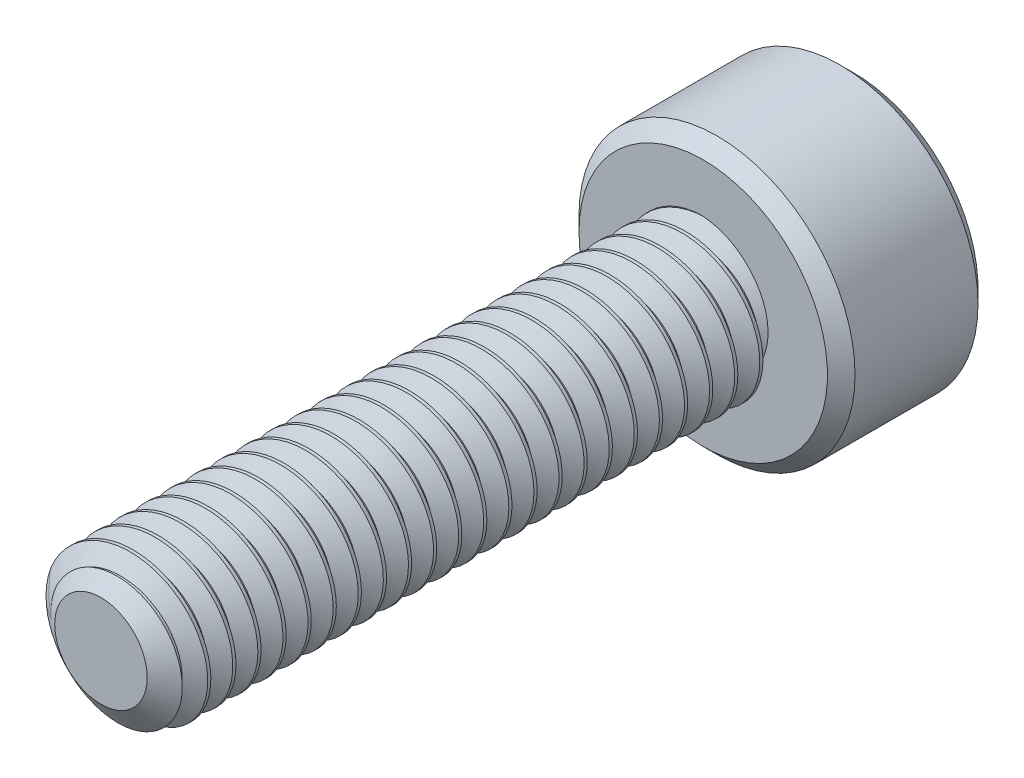
SolidWorks part; units mm, degrees
other "DetailItem1"
ref_plane "Front Plane" through (0, 0, 0) normal (0, 0, 1) x (1, 0, 0)
ref_plane "Top Plane" through (0, 0, 0) normal (0, 1, 0) x (1, 0, 0)
ref_plane "Right Plane" through (0, 0, 0) normal (1, 0, 0) x (0, 0, -1)
sketch "Sketch1" plane through (0, 0, 0) normal (0, 0, 1) x (1, 0, 0)
  circle A0 centre (0, 0) radius 1.5
  dimension "OD" = 3
extrude "Extrude1" add sketch "Sketch1" against normal blind 12
sketch "Sketch2" plane through (0, 0, 0) normal (0, 0, 1) x (1, 0, 0)
  circle A0 centre (0, 0) radius 1.5 construction
  circle A1 centre (0, 0) radius 1.5
curve "Helix/Spiral1" pitch 0.5 height 12.5 radius 1.5 centre (0, 0, 0) axis (0, 0, -1) start towards (0, 1, 0) parameters "pitch"=0.5
sketch "Sketch3" plane through (0, 0, 0) normal (1, 0, 0) x (0, 0, -1)
  line L0 (-0.4375, 1.5) -> (-0.25, 1.1752)
  line L1 (-0.25, 1.1752) -> (-0.1875, 1.1752)
  line L2 (-0.1875, 1.1752) -> (0, 1.5)
  line L3 (-0.4375, 1.5) -> (0, 1.5)
  line L4 (-0.2187, 1.5) -> (-0.2188, 1.1752) construction
  line L5 (-0.3438, 1.3376) -> (-0.0938, 1.3376) construction
  line L6 (0, 1.5) -> (0, -1.5) construction
  dimension "D1" = 0.0625
  dimension "D2" = 0.25
  dimension "D3" = 60
sweep "Cut-Sweep1" cut profiles "Sketch3" path "Helix/Spiral1" align with end faces yes
sketch "Sketch4" plane through (0, 0, 0) normal (1, 0, 0) x (0, 0, -1)
  line L0 (0.4053, 1.5) -> (0, 0.9212)
  line L1 (0, 0.9212) -> (0, 1.5)
  line L2 (0.4053, 1.5) -> (0, 1.5)
  line L3 (-0.4375, 1.5) -> (0, 1.5) construction
  line L4 (0, 0) -> (7.0209, 0) construction
  dimension "D1" = 55
  dimension "D2" = 0.254
revolve "Cut-Revolve1" cut sketch "Sketch4" angle 360 about L4
sketch "Sketch6" plane through (0, 0, -12) normal (0, 0, -1) x (-1, 0, 0)
  circle A0 centre (0, 0) radius 2.75
  dimension "head dia" = 5.5
extrude "Extrude2" add sketch "Sketch6" along normal blind 3
sketch "Sketch7" plane through (0, 0, -15) normal (0, 0, -1) x (-1, 0, 0)
  line L1 (0, 1.4434) -> (-1.25, 0.7217)
  line L2 (-1.25, 0.7217) -> (-1.25, -0.7217)
  line L3 (-1.25, -0.7217) -> (0, -1.4434)
  line L4 (0, -1.4434) -> (1.25, -0.7217)
  line L5 (1.25, -0.7217) -> (1.25, 0.7217)
  line L6 (1.25, 0.7217) -> (0, 1.4434)
  circle A0 centre (0, 0) radius 1.25 construction
  dimension "hex dia" = 2.5
extrude "Cut-Extrude1" cut sketch "Sketch7" against normal blind 1.875
sketch "Sketch8" plane through (0, 0, -15) normal (0, 0, -1) x (-1, 0, 0)
  circle A0 centre (0, 0) radius 1.4434
extrude "Cut-Extrude2" cut sketch "Sketch8" against normal through all draft 45
chamfer "Chamfer1" distance 0.275 angle 45 2 edges at (-2.75, 0, -15) (-2.75, 0, -12)
sketch "Sketch10" plane through (0, 0, -12) normal (0, 0, 1) x (1, 0, 0)
  circle A1 centre (0, 0) radius 1.5
  circle A2 centre (0, 0) radius 1.5
  dimension "D1" = 0
ref_plane "Plane1" through (0, 0, 0) normal (0, 0, 1) x (1, 0, 0)
extrude "partial thread" [suppressed] add sketch "Sketch10" along normal up to surface (4 mm away) separate body up to plane "Plane1"
chamfer "Chamfer2" [suppressed] distance 0.06 angle 45
combine bodies "Combine1" [suppressed] operation type add bodies to combine 107 108
sketch "Sketch9" plane through (0, 0, 0) normal (1, 0, 0) x (0, 0, -1)
  line L0 (0, 1.5) -> (0, -1.5) construction
  line L1 (1.25, 1.5) -> (1.25, -1.5) construction
  dimension "D1" = 1.25
equation "\"D3@Helix/Spiral1\" = \"screw length@Extrude1\"+\"pitch@Helix/Spiral1\""
equation "\"D1@Sketch3\" = \"pitch@Helix/Spiral1\"*.125"
equation "\"D2@Sketch3\" = \"pitch@Helix/Spiral1\"*.5"
equation "\"D1@Cut-Extrude1\" = \"hex dia@Sketch7\"*.75"
equation "\"D1@Chamfer1\" = \"head dia@Sketch6\"*.05"
equation "\"D1@Sketch9\" = \"pitch@Helix/Spiral1\"*2.5"
equation "\"D1@Chamfer2\"=\"OD@Sketch1\"*.02"
